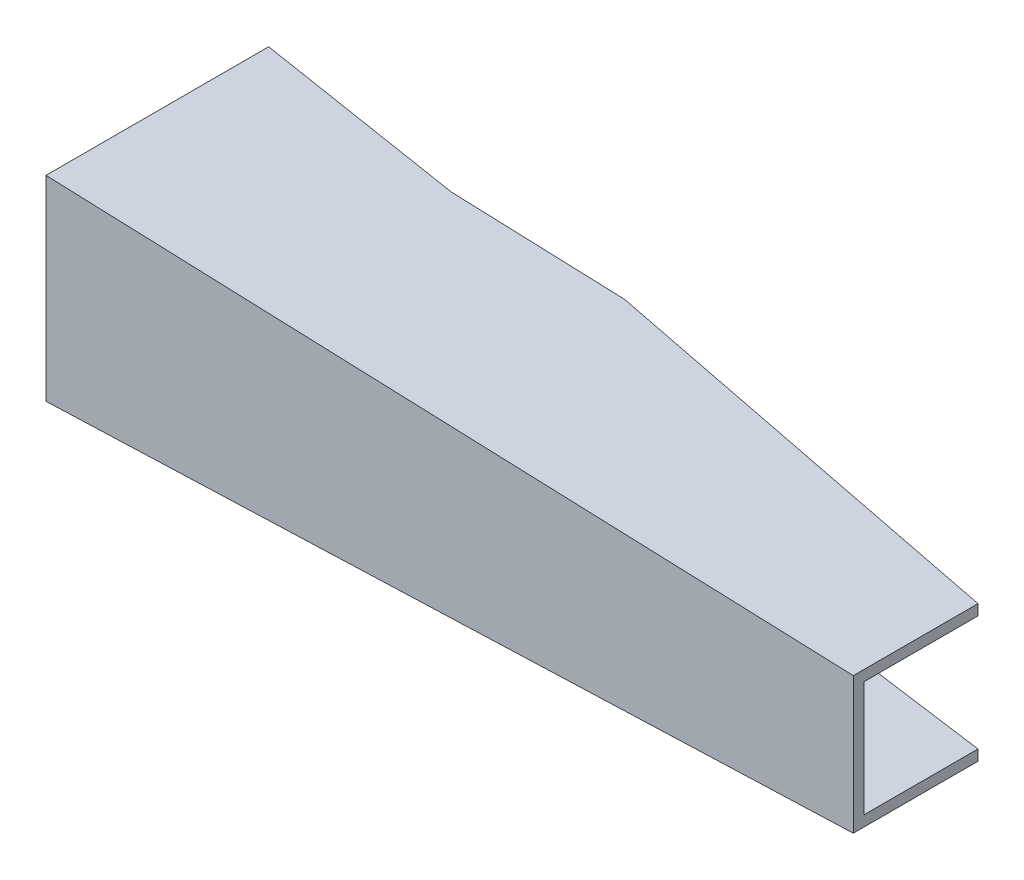
SolidWorks part; units mm, degrees
ref_plane "Front Plane" through (0, 0, 0) normal (0, 0, 1) x (1, 0, 0)
ref_plane "Top Plane" through (0, 0, 0) normal (0, 1, 0) x (1, 0, 0)
ref_plane "Right Plane" through (0, 0, 0) normal (1, 0, 0) x (0, 0, -1)
sketch "Sketch1" plane through (0, 0, 0) normal (0, 0, 1) x (1, 0, 0)
  line L0 (0, 39.555) -> (0, -39.555)
  line L1 (0, -39.555) -> (326.3, -27.585)
  line L2 (326.3, -27.585) -> (326.3, 27.585)
  line L3 (326.3, 27.585) -> (0, 39.555)
  point P4 (0, 0)
  point P6 (326.3, 0)
  dimension "D1" = 326.3
  dimension "D2" = 79.11
  dimension "D3" = 55.17
extrude "Boss-Extrude1" add sketch "Sketch1" along normal blind 105 contours L3 L0 L1 L2
sketch "Sketch3" plane through (0, 0, 0) normal (0, 1, 0) x (1, 0, 0)
  line L0 (0, -15) -> (84.7, -25.82)
  line L1 (84.7, -25.82) -> (154.7, -25.82)
  line L2 (154.7, -25.82) -> (326.3, -54.6)
  line L3 (326.3, -105) -> (326.3, 0) construction
  line L4 (326.3, -105) -> (0, -105) construction
  line L5 (0, -2.365) -> (0, 2.365) construction
  line L6 (0, -15) -> (0, 41.1139)
  line L7 (0, 41.1139) -> (326.3, 36.079)
  line L8 (326.3, 36.079) -> (326.3, -54.6)
  line L9 (0, -105) -> (0, 0) construction
  dimension "D1" = 79.18
  dimension "D2" = 84.7
  dimension "D3" = 70
  dimension "D4" = 50.4
  dimension "D5" = 90
extrude "Cut-Extrude1" cut sketch "Sketch3" against normal blind 105.1 and the other way blind 105.1
sketch "Sketch4" plane through (326.3, 0, 0) normal (1, 0, 0) x (0, 0, -1)
  line L0 (-105, -27.585) -> (-105, 27.585) construction
  line L1 (-100.7, 23.285) -> (-22.5545, 23.285)
  line L2 (-100.7, 23.285) -> (-100.7, -23.285)
  line L3 (-100.7, -23.285) -> (-22.5545, -23.285)
  line L4 (-22.5545, 23.285) -> (-22.5545, -23.285)
  line L5 (-105, 27.585) -> (-54.6, 27.585) construction
  line L6 (-105, -27.585) -> (-54.6, -27.585) construction
  dimension "D1" = 4.3
  dimension "D2" = 4.3
  dimension "D3" = 4.3
sketch "Sketch5" plane through (0, 0, 0) normal (-1, 0, 0) x (0, 0, 1)
  line L0 (105, 39.555) -> (15, 39.555) construction
  line L1 (-10.9565, 35.255) -> (100.7, 35.255)
  line L2 (-10.9565, 35.255) -> (-10.9565, -35.255)
  line L3 (-10.9565, -35.255) -> (100.7, -35.255)
  line L4 (100.7, 35.255) -> (100.7, -35.255)
  line L5 (105, 39.555) -> (105, -39.555) construction
  line L6 (105, -39.555) -> (15, -39.555) construction
  dimension "D1" = 4.3
  dimension "D2" = 4.3
  dimension "D3" = 4.3
loft "Cut-Loft1" cut profiles "Sketch4", "Sketch5" connector at (326.3, 23.285, 100.7) connector at (0, 35.255, 100.7)
sketch "Sketch6" [suppressed] plane through (0, 0, 0) normal (0, 1, 0) x (1, 0, 0)
  line L0 (326.3, -100.7) -> (0, -100.7) construction
  line L1 (-50.6225, 37.8463) -> (354.8737, 37.8463)
  line L2 (-50.6225, 37.8463) -> (-50.6225, -100.7)
  line L3 (-50.6225, -100.7) -> (354.8737, -100.7)
  line L4 (354.8737, 37.8463) -> (354.8737, -100.7)
extrude "Cut-Extrude2" [suppressed] cut sketch "Sketch6" against normal through all and the other way through all
sketch "Sketch7" [suppressed] plane through (1.2916, 35.2076, 0) normal (-0.0367, -0.9993, 0) x (0.9993, -0.0367, 0)
  line L1 (-34.6023, 151.2078) -> (362.4716, 151.2078)
  line L2 (-34.6023, 151.2078) -> (-34.6023, -20.7554)
  line L3 (-34.6023, -20.7554) -> (362.4716, -20.7554)
  line L4 (362.4716, 151.2078) -> (362.4716, -20.7554)
extrude "Cut-Extrude3" [suppressed] cut sketch "Sketch7" along normal through all
equation "\"D2@Sketch4\"=\"D1@Sketch4\""
equation "\"D3@Sketch4\"=\"D1@Sketch4\""
equation "\"D2@Sketch5\"=\"D1@Sketch5\""
equation "\"D3@Sketch5\"=\"D1@Sketch5\""
